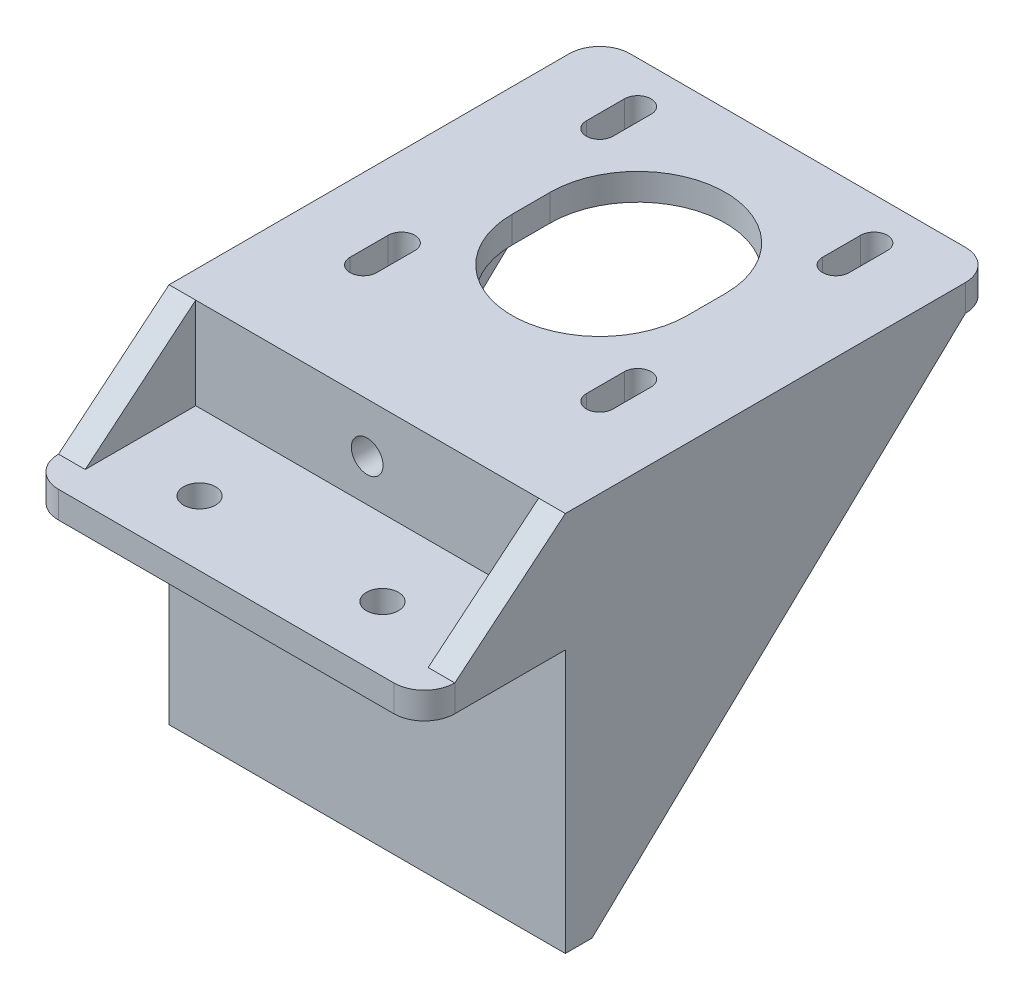
SolidWorks part; units mm, degrees
ref_plane "Front Plane" through (0, 0, 0) normal (0, 0, 1) x (1, 0, 0)
ref_plane "Top Plane" through (0, 0, 0) normal (0, 1, 0) x (1, 0, 0)
ref_plane "Right Plane" through (0, 0, 0) normal (1, 0, 0) x (0, 0, -1)
sketch "Sketch1" plane through (0, 0, 0) normal (0, 1, 0) x (1, 0, 0)
  line L0 (-15.5, 15.5) -> (15.5, -15.5) construction
  line L5 (-26, 0) -> (26, 0) construction
  line L6 (22, 23.5) -> (-22, 23.5)
  line L7 (26, 19.5) -> (26, -47.5)
  line L8 (22, -51.5) -> (-22, -51.5)
  line L9 (-26, 19.5) -> (-26, -47.5)
  line L13 (-12, -43) -> (12, -43) construction
  line L15 (0, -27.5) -> (0, 27.5) construction
  line L16 (0, 2.5) -> (0, -2.5) construction
  line L17 (11.5, 2.5) -> (11.5, -2.5)
  line L18 (-11.5, 2.5) -> (-11.5, -2.5)
  line L19 (-15.5, 18) -> (-15.5, 13) construction
  line L20 (-13.75, 18) -> (-13.75, 13)
  line L21 (-17.25, 18) -> (-17.25, 13)
  line L22 (15.5, 18) -> (15.5, 13) construction
  line L23 (17.25, 18) -> (17.25, 13)
  line L24 (13.75, 18) -> (13.75, 13)
  line L25 (15.5, -13) -> (15.5, -18) construction
  line L26 (17.25, -13) -> (17.25, -18)
  line L27 (13.75, -13) -> (13.75, -18)
  line L28 (-15.5, -13) -> (-15.5, -18) construction
  line L29 (-13.75, -13) -> (-13.75, -18)
  line L30 (-17.25, -13) -> (-17.25, -18)
  circle A1 centre (15.5, 15.5) radius 1.75 construction
  circle A2 centre (-15.5, 15.5) radius 1.75 construction
  circle A3 centre (-15.5, -15.5) radius 1.75 construction
  circle A4 centre (15.5, -15.5) radius 1.75 construction
  arc A9 (-22, -51.5) -> (-26, -47.5) centre (-22, -47.5) cw
  arc A10 (26, -47.5) -> (22, -51.5) centre (22, -47.5) cw
  arc A11 (22, 23.5) -> (26, 19.5) centre (22, 19.5) cw
  arc A12 (-22, 23.5) -> (-26, 19.5) centre (-22, 19.5) ccw
  circle A13 centre (-12, -43) radius 2.1
  circle A14 centre (12, -43) radius 2.1
  arc A15 (11.5, 2.5) -> (-11.5, 2.5) centre (0, 2.5) ccw
  arc A16 (-11.5, -2.5) -> (11.5, -2.5) centre (0, -2.5) ccw
  arc A17 (-13.75, 18) -> (-17.25, 18) centre (-15.5, 18) ccw
  arc A18 (-17.25, 13) -> (-13.75, 13) centre (-15.5, 13) ccw
  arc A19 (17.25, 18) -> (13.75, 18) centre (15.5, 18) ccw
  arc A20 (13.75, 13) -> (17.25, 13) centre (15.5, 13) ccw
  arc A21 (17.25, -13) -> (13.75, -13) centre (15.5, -13) ccw
  arc A22 (13.75, -18) -> (17.25, -18) centre (15.5, -18) ccw
  arc A23 (-13.75, -13) -> (-17.25, -13) centre (-15.5, -13) ccw
  arc A24 (-17.25, -18) -> (-13.75, -18) centre (-15.5, -18) ccw
  point P15 (0, 0)
  point P20 (0, -43)
  point P22 (0, 0)
  point P25 (0, 0)
  point P30 (-15.5, 15.5)
  point P37 (-26, -51.5)
  point P44 (-26, 23.5)
  point P50 (15.5, 15.5)
  point P57 (15.5, -15.5)
  point P64 (-15.5, -15.5)
  dimension "D12" = 5
  dimension "D13" = 3.5
  dimension "D14" = 4
  dimension "D10" = 4.2
  dimension "D6" = 11.5
  dimension "D2" = 31
  dimension "D3" = 31
  dimension "D4" = 52
  dimension "D5" = 75
  dimension "D7" = 8
  dimension "D8" = 8.5
  dimension "D9" = 14
  dimension "D11" = 5
extrude "Boss-Extrude1" add sketch "Sketch1" along normal blind 50
ref_axis "Axis1" through (-12, 50, 43) along (0, -1, 0)
sketch "Sketch2" plane through (0, 0, 0) normal (1, 0, 0) x (0, 0, -1)
  line L0 (38.9254, 0) -> (-38.9254, 0) construction
  line L3 (-51.5, 38) -> (-33, 38)
  line L4 (-33, 50) -> (-33, 38)
  line L7 (23.5, 46.5) -> (-29.5, 46.5)
  line L8 (-29.5, 0) -> (-29.5, 46.5)
  line L10 (-43, 50) -> (-43, 0) construction
  line L11 (23.5, 50) -> (19.5, 50) construction
  line L13 (-47.5, 50) -> (19.5, 50) construction
  line L14 (-51.5, 50) -> (-51.5, 0) construction
  line L16 (23.5, 50) -> (23.5, 0) construction
  line L17 (-51.5, 38) -> (-51.5, 50)
  line L18 (-51.5, 0) -> (-33, 0)
  line L19 (-51.5, 0) -> (-51.5, 34.5)
  line L20 (-51.5, 34.5) -> (-33, 34.5)
  line L21 (-33, 0) -> (-33, 34.5)
  line L22 (-51.5, 50) -> (-33, 50)
  line L23 (23.5, 46.5) -> (23.5, 0)
  line L24 (23.5, 0) -> (-29.5, 0)
  dimension "D1" = 10
  dimension "D2" = 3.5
  dimension "D3" = 3.5
  dimension "D4" = 3.5
  dimension "D5" = 12
extrude "Cut-Extrude1" cut sketch "Sketch2" against normal through all both and the other way through all
sketch "Sketch3" plane through (26, 0, 0) normal (1, 0, 0) x (0, 0, -1)
  line L0 (19.5, 46.5) -> (-29.5, 0)
  line L1 (38.9254, 0) -> (-38.9254, 0) construction
  line L2 (-29.5, 46.5) -> (-29.5, 0) construction
  line L3 (-29.5, 0) -> (-29.5, 46.5)
  line L4 (-29.5, 46.5) -> (19.5, 46.5)
  line L5 (-33, 50) -> (-47.5, 38)
  line L6 (-47.5, 38) -> (-33, 38)
  line L7 (-33, 38) -> (-33, 50)
extrude "Boss-Extrude2" add sketch "Sketch3" against normal blind 3.5
mirror "Mirror1" about plane through (0, 0, 0) normal (1, 0, 0) of "Boss-Extrude2"
sketch "Sketch4" plane through (0, 0, 29.5) normal (0, 0, -1) x (-1, 0, 0)
  line L0 (-12, 24.5) -> (12, 24.5) construction
  line L1 (0, 27.5) -> (0, -27.5) construction
  line L2 (38.9254, 0) -> (-38.9254, 0) construction
  line L5 (22.5, 46.5) -> (-22.5, 46.5) construction
  circle A0 centre (-12, 24.5) radius 2.08
  circle A1 centre (12, 24.5) radius 2.08
  circle A2 centre (0, 43.5) radius 2.08
  point P4 (0, 24.5)
  dimension "D1" = 4.16
  dimension "D4" = 3
  dimension "D2" = 24.5
  dimension "D3" = 12
extrude "Cut-Extrude2" cut sketch "Sketch4" against normal through all
ref_axis "Axis2" through (-12, 24.5, 33) along (0, 0, -1)
ref_axis "Axis3" through (12, 24.5, 33) along (0, 0, -1)
